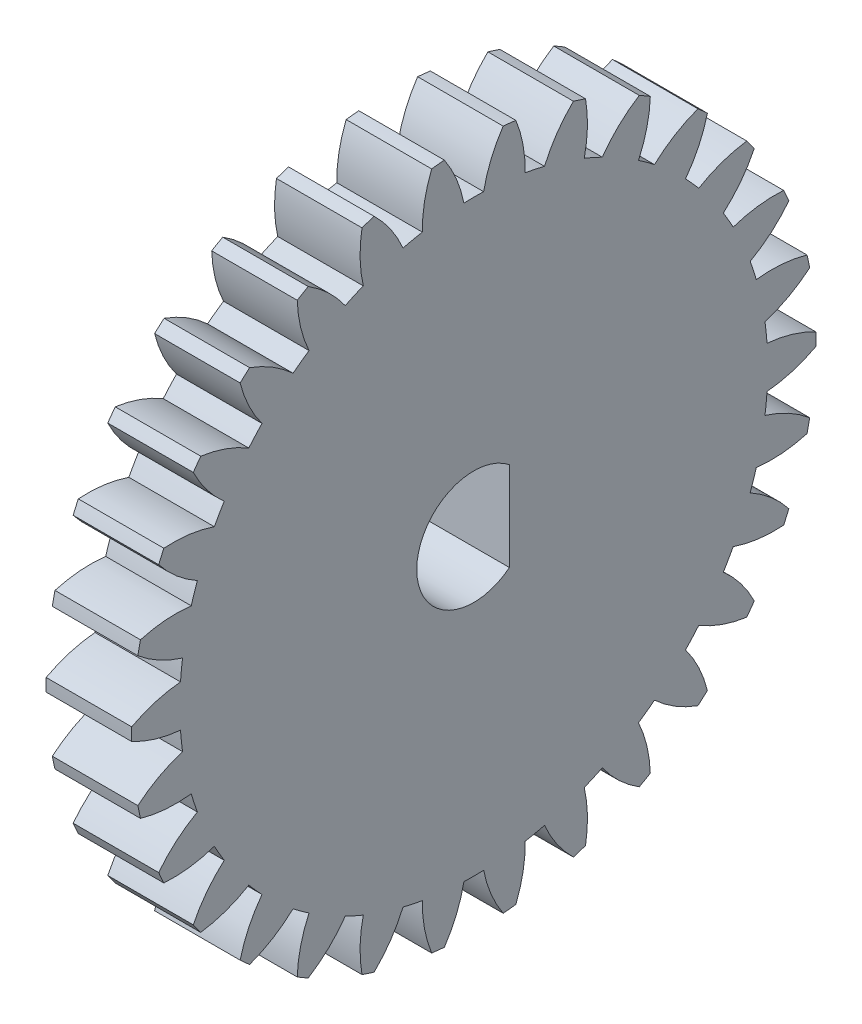
SolidWorks part; units mm, degrees
ref_plane "Plane1" through (0, 0, 0) normal (0, 0, 1) x (1, 0, 0)
ref_plane "Plane2" through (0, 0, 0) normal (0, 1, 0) x (1, 0, 0)
ref_plane "Plane3" through (0, 0, 0) normal (1, 0, 0) x (0, 0, -1)
sketch "HoldingSke" plane through (0, 0, 0) normal (0, 1, 0) x (1, 0, 0)
  line L0 (0, 0) -> (0.5774, -0.3333)
  line L1 (-15, 0) -> (100, 0) construction
  line L2 (0, 0) -> (-2.1039, 2.3779)
  line L3 (0, 0) -> (-11.863, 4.5341)
  line L4 (0, 0) -> (7.479, 4.318)
  line L5 (0, 0) -> (-46.8476, -17.4728)
  line L6 (0, 0) -> (-9.9476, -6.7116)
  line L7 (-2.1039, 2.3779) -> (8.6586, 51.2059)
  line L8 (-76.2, 54.61) -> (-76.1, 54.61)
  line L9 (-71.009, 38.7566) -> (-53.1078, 45.2721)
  line L10 (-76.2, 71.12) -> (104.1128, 71.12)
  line L11 (0, 0) -> (-12, 0)
  line L12 (-76.2, 101.6) -> (-76.147, 101.6)
  line L13 (24.9733, 27.94) -> (52.9518, 28.4284)
  line L14 (24.9733, 27.94) -> (24.9743, 27.94)
  line L15 (24.9733, 27.94) -> (100.4006, 29.5858)
  line L16 (-63.627, -1.5) -> (-12.827, -1.5)
  circle A0 centre (0, 0) radius 0.4
  circle A1 centre (0, 0) radius 20.624
  circle A2 centre (0, 0) radius 37.5
  circle A3 centre (0, 0) radius 0.4
  dimension "MHD" = 41.248
  dimension "Hub_dia" = 75
  dimension "Bore" = 0.8
  dimension "MBD" = 0.8
  dimension "Num_teeth" = 30
  dimension "Pitch_radius" = 180.3128
  dimension "Pitch" = 0.6667
  dimension "Width" = 12
  dimension "Overall_len" = 50
  dimension "Show_teeth" = 30
  dimension "Thickness" = 12
  dimension "OAL" = 50.0001
  dimension "T_dim" = 0.1
  dimension "Ap" = 20
  dimension "H" = 19.05
  dimension "Backlash" = 0.053
  dimension "Addendum_fac" = 1
  dimension "Dedendum_fac" = 1.25
  dimension "Clearance_fac" = 0.25
  dimension "Dedendum_add" = 0.001
  dimension "Module" = 1.5
sketch "BasProSke" plane through (0, 0, 0) normal (0, 1, 0) x (1, 0, 0)
  line L0 (-10, 0) -> (60, 0) construction
  line L1 (0, 0) -> (0, 24)
  line L2 (0, 0) -> (12, 0)
  line L3 (12, 0) -> (12, 24)
  line L4 (12, 24) -> (0, 24)
  dimension "Diameter" = 48
  dimension "Thickness" = 12
revolve "Base-Revolve" add sketch "BasProSke" angle 360 about L0
sketch "TooCutSke" plane through (0, 0, 0) normal (1, 0, 0) x (0, 0, -1)
  line L1 (0, 0) -> (0, 107) construction
  line L2 (0, 0) -> (-1.2703, 22.4641) construction
  line L3 (0, 0) -> (-4.6983, 44.7014) construction
  line L4 (-1.2703, 22.4641) -> (-2.3492, 22.3507) construction
  arc A0 (0.6933, 20.6123) -> (-0.6933, 20.6123) centre (0, 0) ccw
  arc A1 (2.0805, 23.9351) -> (-2.0805, 23.9351) centre (0, 0) ccw
  circle A2 centre (0, 0) radius 22.5 construction
  circle A3 centre (0, 0) radius 21.1431 construction
  arc A4 (-0.6933, 20.6123) -> (-2.0805, 23.9351) centre (-9.5243, 18.8764) ccw
  arc A5 (2.0805, 23.9351) -> (0.6933, 20.6123) centre (9.5243, 18.8764) ccw
  dimension "Root_dia" = 41.248
  dimension "Overcut_dia" = 48.0508
  dimension "Pitch_dia" = 45
  dimension "Base_dia" = 42.2862
  dimension "Flank_rad" = 9
  dimension "Half_ang" = 6
  dimension "Half_CT" = 1.0848
extrude "ToothCut" cut sketch "TooCutSke" along normal through all
fillet "Breaks" [suppressed] radius 0.03 tangent propagation no
fillet "RootFillets" [suppressed] radius 0.376
pattern_circular "TeethCuts" count 30 every 12 about axis through (-10, 0, 0) along (1, 0, 0) of "ToothCut", "RootFillets", "Breaks"
sketch "HubNeaOneSke" plane through (0, 0, 0) normal (-1, 0, 0) x (0, 0, 1)
  circle A0 centre (0, 0) radius 20.624
  dimension "Diameter" = 41.248
extrude "HubNearOne" [suppressed] add sketch "HubNeaOneSke" along normal blind 38.0001
sketch "HubNeaBotSke" plane through (0, 0, 0) normal (-1, 0, 0) x (0, 0, 1)
  circle A0 centre (0, 0) radius 20.624
  dimension "Diameter" = 41.248
extrude "HubNearBoth" [suppressed] add sketch "HubNeaBotSke" along normal blind 19
ref_plane "FarPln" through (12, 0, 0) normal (1, 0, 0) x (0, 0, -1)
sketch "HubFarSke" plane through (12, 0, 0) normal (1, 0, 0) x (0, 0, -1)
  circle A0 centre (0, 0) radius 20.624
  dimension "Diameter" = 41.248
extrude "HubFar" [suppressed] add sketch "HubFarSke" along normal blind 19
sketch "BorSke" plane through (0, 0, 0) normal (1, 0, 0) x (0, 0, -1)
  circle A0 centre (0, 0) radius 0.4
  dimension "Diameter" = 0.8
extrude "Bore" cut sketch "BorSke" along normal mid plane 100.0001
sketch "KeySke" plane through (0, 0, 0) normal (1, 0, 0) x (0, 0, -1)
  line L0 (-0.05, 0) -> (-0.05, 0.5)
  line L1 (-0.05, 0.5) -> (0.05, 0.5)
  line L2 (0.05, 0.5) -> (0.05, 0)
  line L3 (0, 0) -> (0, 34) construction
  line L4 (-0.05, 0) -> (0.05, 0)
  dimension "Offset" = 0.5
  dimension "Width" = 0.1
extrude "Keyway" [suppressed] cut sketch "KeySke" along normal mid plane 100.0001
pattern_circular "Keyway2" [suppressed] count 2 every 90 about axis through (-10, 0, 0) along (1, 0, 0)
sketch "Sketch1" plane through (0, 0, 0) normal (-1, 0, 0) x (0, 0, 1)
  circle A0 centre (-0.4, 0) radius 33.8416
  circle A1 centre (0, 0) radius 0.4 construction
extrude "Cut-Extrude1" cut sketch "Sketch1" against normal offset from surface (6 mm away) 6 up to face at (12, 0, 0)
sketch "Sketch2" plane through (6, 0, 0) normal (-1, 0, 0) x (0, 0, 1)
  line L0 (-2.5, 3.1225) -> (-2.5, -3.1225)
  circle A0 centre (0, 0) radius 4
  dimension "D1" = 8
  dimension "D2" = 2.5
extrude "Cut-Extrude2" cut sketch "Sketch2" against normal blind 6 contours L0 A0 region at (6, 0, 0.464)
equation "' \"Module@HoldingSke\" = 6.35"
equation "' \"Num_teeth@HoldingSke\" = 12"
equation "' \"Ap@HoldingSke\" =  20"
equation "' \"Width@HoldingSke\" = 0.5 * 25.4"
equation "' \"Hub_dia@HoldingSke\"= 1 * 25.4"
equation "' \"Overall_len@HoldingSke\" = 1.0 * 25.4"
equation "' \"Bore@HoldingSke\" = 0.75 * 25.4"
equation "' \"T_dim@HoldingSke\" = 0.1 * 25.4"
equation "' \"Width@KeySke\" = 0.25 * 25.4"
equation "' \"Show_teeth@HoldingSke\" = 13"
equation "' \"Backlash@HoldingSke\" = 0.009 * 25.4"
equation "' \"Addendum_fac@HoldingSke\" = 1.0"
equation "' \"Dedendum_fac@HoldingSke\" = 1.25"
equation "' \"Dedendum_add@HoldingSke\" = 0.00005 * 25.4"
equation "' \"Clearance_fac@HoldingSke\" = 0.25"
equation "\"Pitch@HoldingSke\" = 1 / \"Module@HoldingSke\""
equation "\"Overcut_dia@TooCutSke\" = (\"Num_teeth@HoldingSke\" + 2 * \"Addendum_fac@HoldingSke\") / \"Pitch@HoldingSke\" + 0.002 * 25.4"
equation "\"Pitch_dia@TooCutSke\" = \"Num_teeth@HoldingSke\" / \"Pitch@HoldingSke\""
equation "\"Base_dia@TooCutSke\" = \"Num_teeth@HoldingSke\" / \"Pitch@HoldingSke\" * cos((\"Ap@HoldingSke\"  * 3.14159265 / 180))"
equation "\"Root_dia@TooCutSke\" = (\"Num_teeth@HoldingSke\" + 2) / \"Pitch@HoldingSke\" - 2 * (\"Addendum_fac@HoldingSke\" + \"Dedendum_fac@HoldingSke\") / \"Pitch@HoldingSke\" - \"Dedendum_add@HoldingSke\" * 2"
equation "\"Half_ang@TooCutSke\" = 180 / \"Num_teeth@HoldingSke\""
equation "\"Half_CT@TooCutSke\" = \"Num_teeth@HoldingSke\" / \"Pitch@HoldingSke\" * sin((3.14159265 / 2 / \"Num_teeth@HoldingSke\")) / 2 - 7 * \"Backlash@HoldingSke\" / 4"
equation "\"Flank_rad@TooCutSke\" = \"Num_teeth@HoldingSke\" / \"Pitch@HoldingSke\" / 5"
equation "\"Radius@RootFillets\" = \"Clearance_fac@HoldingSke\" / \"Pitch@HoldingSke\" + \"Dedendum_add@HoldingSke\""
equation "\"Break_rad@Breaks\" = 0.02 / \"Pitch@HoldingSke\""
equation "\"Thickness@HoldingSke\" = \"Width@HoldingSke\""
equation "\"OAL@HoldingSke\" = \"Thickness@HoldingSke\""
equation "\"MHD@HoldingSke\" = (\"Num_teeth@HoldingSke\" + 2) / \"Pitch@HoldingSke\" - 2 * (\"Addendum_fac@HoldingSke\" + \"Dedendum_fac@HoldingSke\")  / \"Pitch@HoldingSke\" - \"Dedendum_add@HoldingSke\" * 2"
equation "\"MBD@HoldingSke\" = (\"Num_teeth@HoldingSke\" + 2) / \"Pitch@HoldingSke\" - 2 * (\"Addendum_fac@HoldingSke\" + \"Dedendum_fac@HoldingSke\")  / \"Pitch@HoldingSke\" - \"Dedendum_add@HoldingSke\" * 2 - 0.002 * 25.4"
equation "\"MHD@HoldingSke\" = ((sgn( \"MHD@HoldingSke\" - \"Hub_dia@HoldingSke\" )-1)*( \"MHD@HoldingSke\" - \"Hub_dia@HoldingSke\" ))/-2+ \"Hub_dia@HoldingSke\""
equation "\"MBD@HoldingSke\" = ((sgn( \"MBD@HoldingSke\" - \"Bore@HoldingSke\" )-1)*( \"MBD@HoldingSke\" - \"Bore@HoldingSke\" ))/-2+ \"Bore@HoldingSke\""
equation "\"OAL@HoldingSke\" = ((sgn( \"OAL@HoldingSke\" - \"Overall_len@HoldingSke\" )+1)*( \"OAL@HoldingSke\" - \"Overall_len@HoldingSke\" ))/2 + \"Overall_len@HoldingSke\" + 0.000002 * 25.4"
equation "\"Num_teeth@TeethCuts\" = int( \"Show_teeth@HoldingSke\" ) + 1"
equation "\"Num_teeth@TeethCuts\" = ((sgn( \"Num_teeth@TeethCuts\" - \"Num_teeth@HoldingSke\" )-1)*( \"Num_teeth@TeethCuts\" - \"Num_teeth@HoldingSke\" ))/-2+ \"Num_teeth@HoldingSke\""
equation "\"Num_teeth@TeethCuts\" = ((sgn( \"Num_teeth@TeethCuts\" - 2.0)+1)*( \"Num_teeth@TeethCuts\" - 2.0))/2 +2.0"
equation "\"Angle@TeethCuts\" = 360.0 / \"Num_teeth@HoldingSke\""
equation "\"Diameter@BasProSke\" = (\"Num_teeth@HoldingSke\" + 2 * \"Addendum_fac@HoldingSke\") / \"Pitch@HoldingSke\""
equation "\"Thickness@BasProSke\"  = \"Thickness@HoldingSke\""
equation "' \"Fillet_rad@BasProSke\" =  \"Thickness@HoldingSke\" * 0.05"
equation "\"MHD@HoldingSke\" = ((sgn( \"MHD@HoldingSke\" - \"Root_dia@TooCutSke\" )-1)*( \"MHD@HoldingSke\" - \"Root_dia@TooCutSke\" ))/-2+ \"Root_dia@TooCutSke\""
equation "\"Diameter@HubNeaOneSke\" = \"MHD@HoldingSke\""
equation "\"Length@HubNearOne\" = \"OAL@HoldingSke\" - \"Thickness@BasProSke\""
equation "\"Diameter@HubNeaBotSke\" = \"MHD@HoldingSke\""
equation "\"Length@HubNearBoth\" = ( \"OAL@HoldingSke\" - \"Thickness@BasProSke\" ) / 2.0"
equation "\"Thickness@FarPln\" = \"Thickness@BasProSke\""
equation "\"Diameter@HubFarSke\" = \"MHD@HoldingSke\""
equation "\"Length@HubFar\" = ( \"OAL@HoldingSke\" - \"Thickness@BasProSke\" ) / 2.0"
equation "\"Diameter@BorSke\" = \"MBD@HoldingSke\""
equation "\"D1@Bore\" = \"OAL@HoldingSke\" * 2.0"
equation "\"D1@Keyway\" = \"OAL@HoldingSke\" * 2.0"
equation "\"Offset@KeySke\" = \"T_dim@HoldingSke\" + \"MBD@HoldingSke\" / 2.0"
